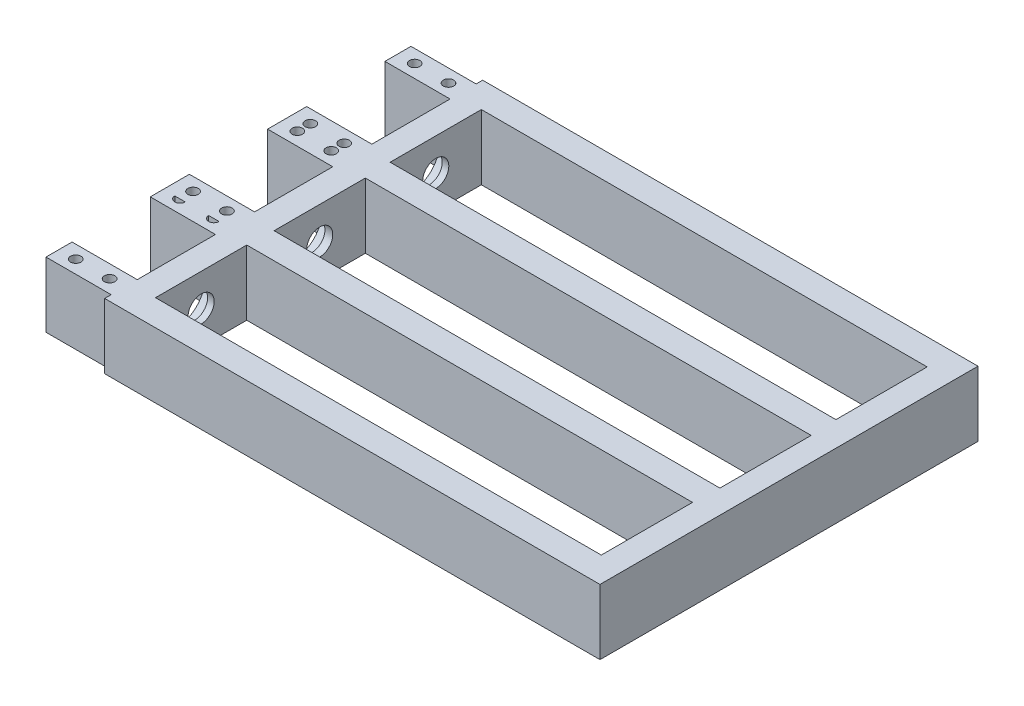
SolidWorks part; units mm, degrees
ref_plane "Płaszczyzna przednia" through (0, 0, 0) normal (0, 0, 1) x (1, 0, 0)
ref_plane "Płaszczyzna górna" through (0, 0, 0) normal (0, 1, 0) x (1, 0, 0)
ref_plane "Płaszczyzna prawa" through (0, 0, 0) normal (1, 0, 0) x (0, 0, -1)
sketch "Szkic1" plane through (0, 0, 0) normal (0, 1, 0) x (1, 0, 0)
  line L1 (-95, 72.5) -> (95, 72.5)
  line L2 (-95, 72.5) -> (-95, -72.5)
  line L3 (-95, -72.5) -> (95, -72.5)
  line L4 (95, 72.5) -> (95, -72.5)
  line L5 (-95, 72.5) -> (95, -72.5) construction
  line L6 (-95, -72.5) -> (95, 72.5) construction
  point P0 (0, 0)
  dimension "D1" = 145
  dimension "D2" = 190
extrude "Dodanie-wyciągnięcie1" add sketch "Szkic1" along normal blind 25
sketch "Szkic2" plane through (0, 25, 0) normal (0, 1, 0) x (1, 0, 0)
  line L0 (-95, 0) -> (95, 0) construction
  line L1 (-95, 72.5) -> (-95, -72.5) construction
  line L2 (95, -72.5) -> (95, 72.5) construction
  line L3 (0, 0) -> (0, -72.5) construction
  line L4 (-85, -17.5) -> (86, -17.5)
  line L5 (-85, -17.5) -> (-85, 17.5)
  line L6 (-85, 17.5) -> (86, 17.5)
  line L7 (86, -17.5) -> (86, 17.5)
  line L8 (-85, -17.5) -> (86, 17.5) construction
  line L9 (-85, 17.5) -> (86, -17.5) construction
  line L10 (-95, -72.5) -> (95, -72.5) construction
  line L11 (-85.5, 27.5) -> (85.5, 62.5) construction
  line L12 (-85.5, -62.5) -> (85.5, -62.5)
  line L13 (-85.5, -62.5) -> (-85.5, -27.5)
  line L14 (-85.5, -27.5) -> (85.5, -27.5)
  line L15 (85.5, -62.5) -> (85.5, -27.5)
  line L16 (-85.5, -62.5) -> (85.5, -27.5) construction
  line L17 (-85.5, -27.5) -> (85.5, -62.5) construction
  line L18 (-85.5, 62.5) -> (85.5, 27.5) construction
  line L19 (85.5, 62.5) -> (85.5, 27.5)
  line L20 (-85.5, 27.5) -> (85.5, 27.5)
  line L21 (-85.5, 62.5) -> (-85.5, 27.5)
  line L22 (-85.5, 62.5) -> (85.5, 62.5)
  point P6 (0.5, 0)
  point P15 (0, -45)
  point P24 (0, 45)
  dimension "D1" = 35
  dimension "D2" = 9
  dimension "D3" = 10
  dimension "D4" = 10
  dimension "D5" = 35
extrude "Wytnij-wyciągnięcie1" cut sketch "Szkic2" against normal blind 50
sketch "Szkic3" plane through (85.5, 0, 0) normal (-1, 0, 0) x (0, 0, 1)
  line L0 (27.5, 12.5) -> (62.5, 12.5) construction
  line L1 (27.5, 0) -> (27.5, 25) construction
  line L2 (62.5, 0) -> (62.5, 25) construction
  circle A0 centre (45, 12.5) radius 11
  point P8 (39.4823, 12.5842)
  point P9 (27.5, 12.9964)
  point P10 (27.5, 12.5)
  dimension "D1" = 22
  dimension "D2" = 17.5
extrude "Wytnij-wyciągnięcie2" cut sketch "Szkic3" against normal blind 7
sketch "Szkic4" plane through (-95, 0, 0) normal (-1, 0, 0) x (0, 0, 1)
  circle A0 centre (45, 12.5) radius 11 construction
  circle A1 centre (45, 12.5) radius 11
extrude "Wytnij-wyciągnięcie3" cut sketch "Szkic4" against normal blind 7
sketch "Szkic5" plane through (-88, 0, 0) normal (-1, 0, 0) x (0, 0, 1)
  circle A0 centre (45, 12.5) radius 5
  point P2 (39.5, 12.5)
  point P3 (42.5, 12.5)
  point P4 (45, 12.5)
  dimension "D1" = 10
extrude "Wytnij-wyciągnięcie4" cut sketch "Szkic5" against normal blind 7
sketch "Szkic7" plane through (0, 25, 0) normal (0, 1, 0) x (1, 0, 0)
  line L0 (-95, 72.5) -> (-95, -72.5) construction
  line L1 (-95, -70) -> (-120, -70)
  line L2 (-95, -70) -> (-95, -60)
  line L3 (-95, -60) -> (-120, -60)
  line L4 (-120, -70) -> (-120, -60)
  line L5 (-85.5, -50) -> (-85.5, -40) construction
  line L6 (-95, -30) -> (-120, -30)
  line L7 (-95, -30) -> (-95, -20)
  line L8 (-95, -20) -> (-120, -20)
  line L9 (-120, -30) -> (-120, -20)
  line L10 (-85.5, -50) -> (-85.5, -40)
  line L11 (-85.5, -45) -> (-183.1039, -45) construction
  line L12 (-95, -30) -> (-95, -60) construction
  line L13 (95, -72.5) -> (95, 72.5) construction
  point P14 (-95, -45)
  line M24 (-95, 72.5) -> (-95, -72.5)
  dimension "D1" = 30
  dimension "D2" = 10
  dimension "D3" = 215
extrude "Dodanie-wyciągnięcie2" add sketch "Szkic7" against normal up to vertex (25 mm away) contours L9 L6 L8 M24 | L4 L1 L3 M24 region at (-107.5, 25, 25) region at (-107.5, 25, 65) up to point (-95, 0, 72.5)
sketch "Szkic8" plane through (0, 25, 0) normal (0, 1, 0) x (1, 0, 0)
  line L0 (-113.6, -25) -> (-100.6, -25) construction
  line L1 (-113.6, -25) -> (-120, -25) construction
  line L2 (-120, -30) -> (-120, -20) construction
  line L3 (-95, -45) -> (-185.7611, -45) construction
  line L4 (-95, -30) -> (-95, -60) construction
  circle A2 centre (-100.6, -25) radius 2
  circle A3 centre (-113.6, -25) radius 2
  circle A4 centre (-100.6, -65) radius 2
  circle A5 centre (-113.6, -65) radius 2
  dimension "D2" = 100.6
  dimension "D3" = 4
  dimension "D1" = 13
extrude "Wytnij-wyciągnięcie5" cut sketch "Szkic8" against normal blind 12
pattern_linear "Szyk liniowy1" count 3 spacing 45 along (0, 0, -1) of "Wytnij-wyciągnięcie5", "Dodanie-wyciągnięcie2", "Wytnij-wyciągnięcie4", "Wytnij-wyciągnięcie3", "Wytnij-wyciągnięcie2"
